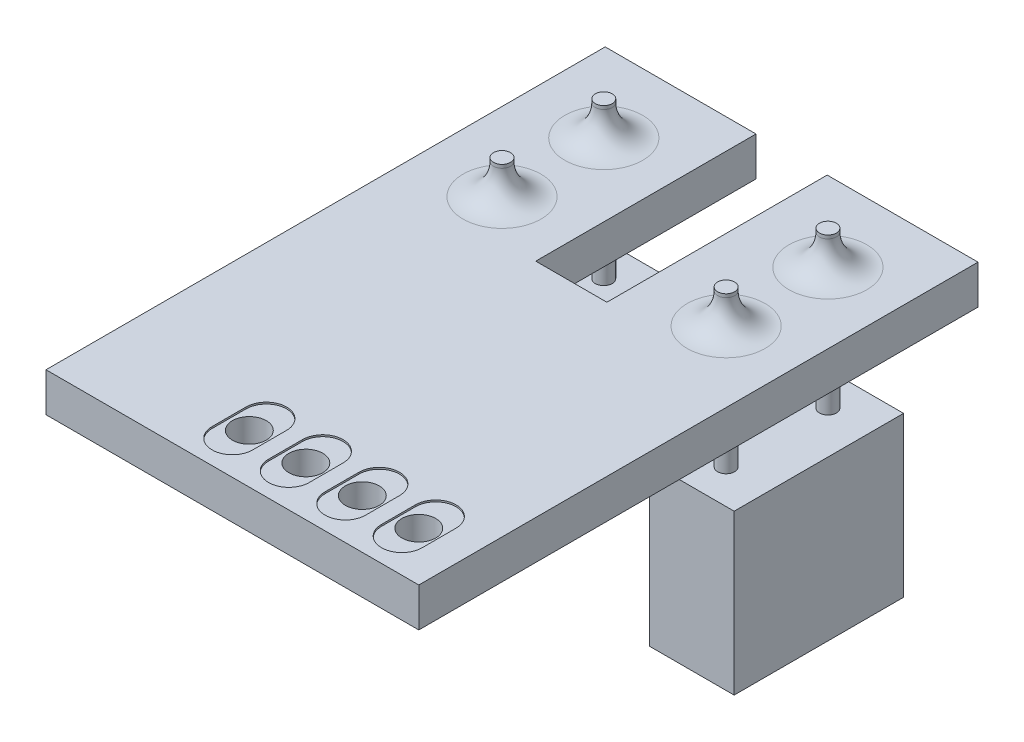
SolidWorks part; units mm, degrees
ref_plane "Front Plane" through (0, 0, 0) normal (0, 0, 1) x (1, 0, 0)
ref_plane "Top Plane" through (0, 0, 0) normal (0, 1, 0) x (1, 0, 0)
ref_plane "Right Plane" through (0, 0, 0) normal (1, 0, 0) x (0, 0, -1)
sketch "Sketch1" plane through (0, 0, 0) normal (0, 1, 0) x (1, 0, 0)
  line L0 (0, 0) -> (0, 16.5)
  line L1 (0, 16.5) -> (4.45, 16.5)
  line L2 (4.45, 16.5) -> (4.45, 10)
  line L3 (4.45, 10) -> (6.55, 10)
  line L4 (6.55, 10) -> (6.55, 16.5)
  line L5 (6.55, 16.5) -> (11, 16.5)
  line L6 (11, 16.5) -> (11, 0)
  line L7 (11, 0) -> (0, 0)
  line L8 (4.5, 1.5) -> (6.1667, 1.5) construction
  line L9 (6.1667, 1.5) -> (7.8333, 1.5) construction
  line L10 (7.8333, 1.5) -> (9.5, 1.5) construction
  circle A0 centre (9.5, 1.5) radius 0.5
  circle A1 centre (7.8333, 1.5) radius 0.5
  circle A2 centre (6.1667, 1.5) radius 0.5
  circle A3 centre (4.5, 1.5) radius 0.5
  dimension "D8" = 1
  dimension "D1" = 11
  dimension "D2" = 16.5
  dimension "D3" = 2.1
  dimension "D4" = 6.5
  dimension "D5" = 1.5
  dimension "D6" = 1.5
  dimension "D7" = 5
extrude "Boss-Extrude1" add sketch "Sketch1" along normal blind 1.15
sketch "Sketch2" plane through (0, 1.15, 0) normal (0, 1, 0) x (1, 0, 0)
  circle A0 centre (2.3033, 14.155) radius 0.25
  circle A1 centre (2.3033, 11.1517) radius 0.25
  circle A2 centre (8.9166, 11.1517) radius 0.25
  circle A3 centre (8.9166, 14.155) radius 0.25
  dimension "D1" = 0.5
extrude "Boss-Extrude2" add sketch "Sketch2" along normal blind 1 and the other way blind 3.6
sketch "Sketch3" plane through (0, -2.45, 0) normal (0, -1, 0) x (1, 0, 0)
  line L1 (1.0533, -10.1379) -> (3.5533, -10.1379)
  line L2 (1.0533, -10.1379) -> (1.0533, -15.1379)
  line L3 (1.0533, -15.1379) -> (3.5533, -15.1379)
  line L4 (3.5533, -10.1379) -> (3.5533, -15.1379)
  line L5 (7.6666, -10.1379) -> (10.1666, -10.1379)
  line L6 (7.6666, -10.1379) -> (7.6666, -15.1379)
  line L7 (7.6666, -15.1379) -> (10.1666, -15.1379)
  line L8 (10.1666, -10.1379) -> (10.1666, -15.1379)
  point P8 (2.3033, -11.1517)
  point P9 (2.3033, -10.1379)
  point P11 (8.9166, -11.1517)
  point P12 (8.9166, -10.1379)
  dimension "D1" = 5
  dimension "D2" = 2.5
extrude "Boss-Extrude3" add sketch "Sketch3" along normal blind 4.7
sketch "Sketch4" plane through (0, 1.15, 0) normal (0, 1, 0) x (1, 0, 0)
  line L0 (4.5, 1) -> (4.5, 2) construction
  line L1 (3.9018, 1) -> (3.9018, 2)
  line L2 (5.0982, 1) -> (5.0982, 2)
  line L3 (6.1667, 1) -> (6.1667, 2) construction
  line L4 (5.5685, 1) -> (5.5685, 2)
  line L5 (6.7649, 1) -> (6.7649, 2)
  line L6 (7.8333, 1) -> (7.8333, 2) construction
  line L7 (7.2351, 1) -> (7.2351, 2)
  line L8 (8.4315, 1) -> (8.4315, 2)
  line L9 (9.5, 1) -> (9.5, 2) construction
  line L10 (8.9018, 1) -> (8.9018, 2)
  line L11 (10.0982, 1) -> (10.0982, 2)
  arc A0 (3.9018, 1) -> (5.0982, 1) centre (4.5, 1) ccw
  arc A1 (5.0982, 2) -> (3.9018, 2) centre (4.5, 2) ccw
  arc A2 (5.5685, 1) -> (6.7649, 1) centre (6.1667, 1) ccw
  arc A3 (6.7649, 2) -> (5.5685, 2) centre (6.1667, 2) ccw
  arc A4 (7.2351, 1) -> (8.4315, 1) centre (7.8333, 1) ccw
  arc A5 (8.4315, 2) -> (7.2351, 2) centre (7.8333, 2) ccw
  arc A6 (8.9018, 1) -> (10.0982, 1) centre (9.5, 1) ccw
  arc A7 (10.0982, 2) -> (8.9018, 2) centre (9.5, 2) ccw
  circle A8 centre (4.5, 1.5) radius 0.5 construction
  point P2 (4.5, 1.5)
  point P9 (6.1667, 1.5)
  point P17 (7.8333, 1.5)
  point P25 (9.5, 1.5)
extrude "Cut-Extrude1" cut sketch "Sketch4" against normal blind 0.05
fillet "Fillet1" radius 0.9 4 edges at (8.9166, 1.15, -14.405) (8.9166, 1.15, -11.4017) (2.3033, 1.15, -14.405) (2.3033, 1.15, -11.4017)
sketch "Sketch5" plane through (0, 0, 0) normal (1, 0, 0) x (0, 0, -1)
  line L0 (15.1379, -7.15) -> (15.1379, -2.45) construction
  line L1 (15.1379, -2.45) -> (10.1379, -2.45) construction
  point P0 (17.1379, -4.8)
  point P1 (15.1379, -4.8)
  point P2 (12.6379, -4.8)
  point P5 (12.6379, -2.45)
  point P8 (8.1379, -4.8)
  dimension "D1" = 4.5
  dimension "D2" = 4.5
ref_axis "Axis1" through (0, -4.8, -17.1379) along (1, 0, 0)
ref_axis "new axis" through (0, -4.8, -8.1379) along (-1, 0, 0)
ref_plane "Plane1" through (0, 0, -12.6379) normal (0, 0, -1) x (-1, 0, 0)
ref_plane "Plane3" through (0, -4.8, 0) normal (0, 1, 0) x (1, 0, 0)
ref_plane "Plane2" through (0, -2.8, 0) normal (0, 1, 0) x (1, 0, 0)
